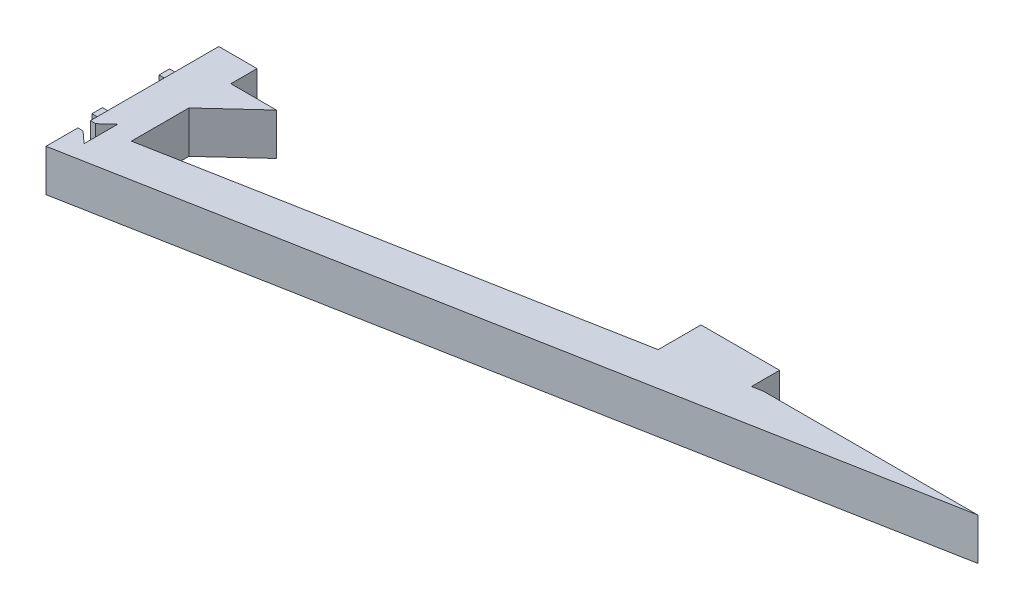
SolidWorks part; units mm, degrees
ref_plane "Přední rovina" through (0, 0, 0) normal (0, 0, 1) x (1, 0, 0)
ref_plane "Horní rovina" through (0, 0, 0) normal (0, 1, 0) x (1, 0, 0)
ref_plane "Pravá rovina" through (0, 0, 0) normal (1, 0, 0) x (0, 0, -1)
sketch "Skica1" plane through (0, 0, 0) normal (0, 1, 0) x (1, 0, 0)
  line L0 (0, 0) -> (0, -32.97)
  line L1 (0, -32.97) -> (149.85, -5)
  line L2 (149.85, -5) -> (108.9746, -5)
  line L3 (108.9746, -5) -> (107, -5.3686)
  line L4 (107, -5.3686) -> (107, 0)
  line L5 (107, 0) -> (92, 0)
  line L6 (92, 0) -> (92, -8.1684)
  line L7 (92, -8.1684) -> (7.3, -23.9779)
  line L8 (7.3, -23.9779) -> (7.3, 0)
  line L9 (7.3, 0) -> (0, 0)
  point P3 (92, -4.0842)
  dimension "D1" = 32.97
  dimension "D2" = 7.3
  dimension "D3" = 15
  dimension "D4" = 5
  dimension "D5" = 7.5
  dimension "D6" = 7.5
  dimension "D7" = 84.7
  dimension "D8" = 149.85
extrude "Přidat vysunutím1" add sketch "Skica1" along normal blind 8
sketch "Skica2" plane through (0, 8, 0) normal (0, 1, 0) x (1, 0, 0)
  line L6 (0, -24.5) -> (1, -24.5)
  line L7 (0, 0) -> (0, -32.97) construction
  line L8 (1, -24.5) -> (3.2, -22.5)
  line L9 (3.2, -22.5) -> (3.2, -28.9)
  line L10 (3.2, -28.9) -> (1, -26.9)
  line L11 (1, -26.9) -> (0, -26.9)
  line L12 (0, -26.9) -> (0, -24.5)
  line L13 (7.3, 0) -> (0, 0) construction
  dimension "D1" = 1
  dimension "D2" = 1
  dimension "D3" = 3.2
  dimension "6,8" = 6.4
  dimension "2,8" = 2.4
  dimension "D4" = 2
  dimension "4" = 22.5
extrude "Odebrat vysunutím1" cut sketch "Skica2" against normal through all
sketch "Skica3" plane through (0, 0, 0) normal (-1, 0, 0) x (0, 0, 1)
  line L1 (5.4, 5) -> (7.4, 5)
  line L2 (5.4, 5) -> (5.4, 3)
  line L3 (5.4, 3) -> (7.4, 3)
  line L4 (7.4, 5) -> (7.4, 3)
  line L5 (18.2, 5) -> (20.2, 5)
  line L6 (18.2, 5) -> (18.2, 3)
  line L7 (18.2, 3) -> (20.2, 3)
  line L8 (20.2, 5) -> (20.2, 3)
  line L13 (0, 8) -> (0, 0) construction
  line L14 (0, 8) -> (24.5, 8) construction
  dimension "D1" = 2
  dimension "D2" = 2
  dimension "D3" = 2
  dimension "D4" = 2
  dimension "D7" = 5.4
  dimension "D8" = 3
  dimension "D9" = 3
  dimension "D11" = 10.8
extrude "Přidat vysunutím2" add sketch "Skica3" along normal blind 4
sketch "Skica5" plane through (0, 8, 0) normal (0, 1, 0) x (1, 0, 0)
  line L0 (0, 0) -> (0, -24.5) construction
  line L5 (0, -5) -> (16, -5)
  line L6 (0, -5) -> (0, -13)
  line L7 (0, -13) -> (16, -13)
  line L8 (16, -5) -> (16, -13)
  line L9 (7.3, 0) -> (0, 0) construction
  dimension "D1" = 8
  dimension "D2" = 5
  dimension "D3" = 16
extrude "Přidat vysunutím4" add sketch "Skica5" against normal blind 8
sketch "Skica7" plane through (0, 0, 0) normal (0, -1, 0) x (1, 0, 0)
  line L3 (7.3, 13) -> (16, 13)
  line L4 (16, 13) -> (16, 5)
  line L5 (16, 5) -> (7.3, 13)
extrude "Odebrat vysunutím3" cut sketch "Skica7" against normal through all
